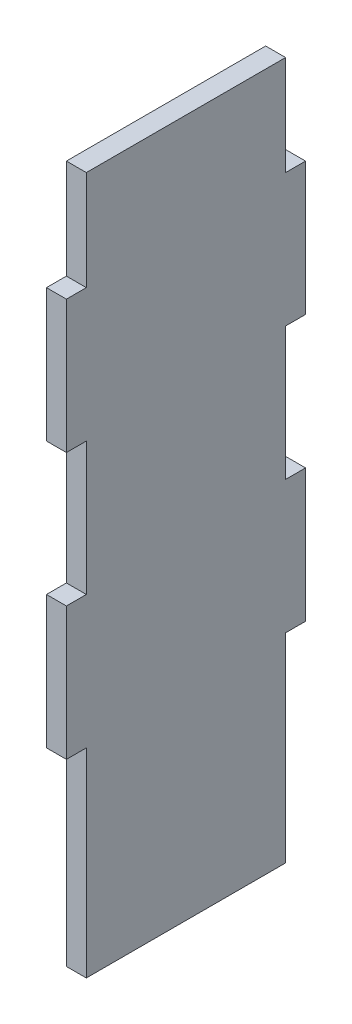
SolidWorks part; units mm, degrees
material "Acrilico TEC"
ref_plane "Front Plane" through (0, 0, 0) normal (0, 0, 1) x (1, 0, 0)
ref_plane "Top Plane" through (0, 0, 0) normal (0, 1, 0) x (1, 0, 0)
ref_plane "Right Plane" through (0, 0, 0) normal (1, 0, 0) x (0, 0, -1)
sketch "Sketch1" plane through (0, 0, 0) normal (1, 0, 0) x (0, 0, -1)
  line L0 (-15, 0) -> (15, 0)
  line L1 (15, 0) -> (15, 30)
  line L2 (15, 30) -> (18, 30)
  line L3 (18, 30) -> (18, 50)
  line L4 (18, 50) -> (15, 50)
  line L5 (15, 50) -> (15, 70)
  line L6 (15, 70) -> (18, 70)
  line L7 (18, 70) -> (18, 90)
  line L8 (18, 90) -> (15, 90)
  line L9 (15, 90) -> (15, 105)
  line L10 (15, 105) -> (-15, 105)
  line L11 (0, 105) -> (0, 0) construction
  line L12 (-15, 90) -> (-15, 105)
  line L13 (-18, 90) -> (-15, 90)
  line L14 (-18, 70) -> (-18, 90)
  line L15 (-15, 70) -> (-18, 70)
  line L16 (-15, 50) -> (-15, 70)
  line L17 (-18, 50) -> (-15, 50)
  line L18 (-18, 30) -> (-18, 50)
  line L19 (-15, 30) -> (-18, 30)
  line L20 (-15, 0) -> (-15, 30)
  dimension "D1" = 15
  dimension "D2" = 30
  dimension "D3" = 20
  dimension "D4" = 20
  dimension "D5" = 20
  dimension "D6" = 15
  dimension "D7" = 3
extrude "Boss-Extrude1" add sketch "Sketch1" along normal blind 3
